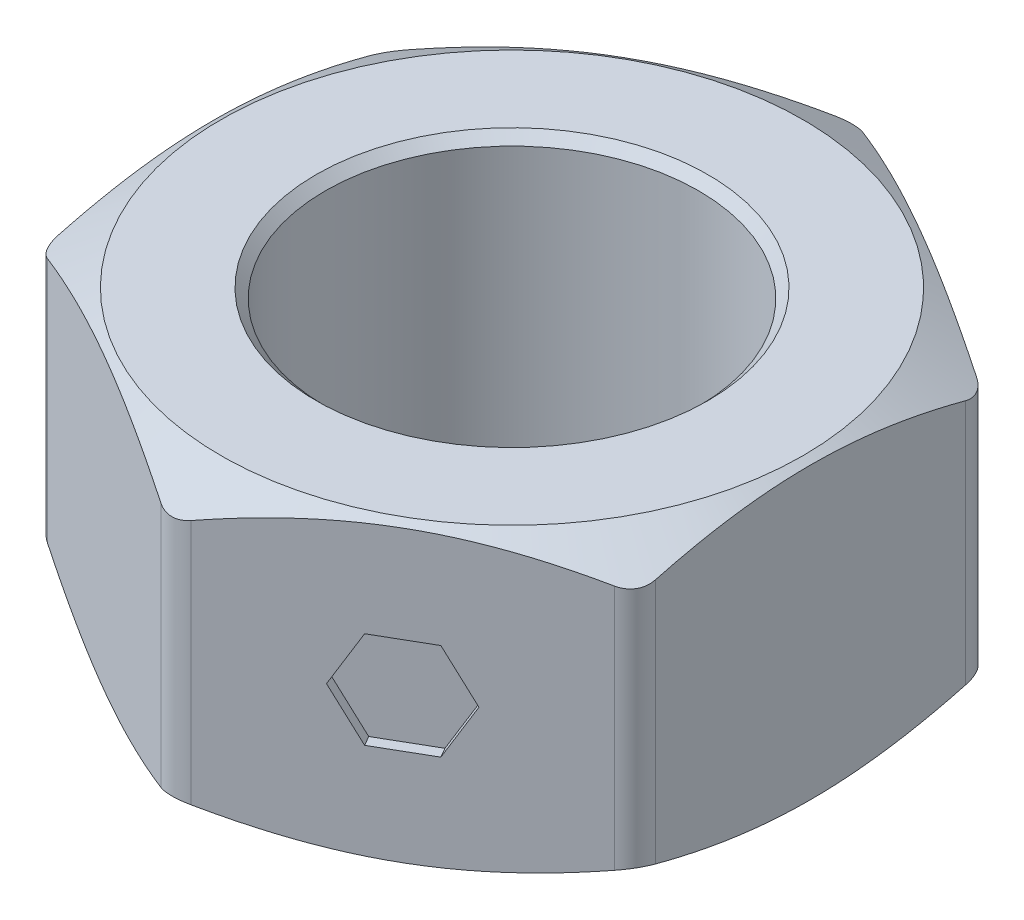
SolidWorks part; units mm, degrees
ref_plane "Front Plane" through (0, 0, 0) normal (0, 0, 1) x (1, 0, 0)
ref_plane "Top Plane" through (0, 0, 0) normal (0, 1, 0) x (1, 0, 0)
ref_plane "Right Plane" through (0, 0, 0) normal (1, 0, 0) x (0, 0, -1)
sketch "Sketch1" plane through (0, 0, 0) normal (0, 0, 1) x (1, 0, 0)
  line L0 (0, -2) -> (0, 2) construction
  line L1 (4, 0) -> (-4, 0) construction
  line L2 (2.5, -2) -> (-2.5, -2) construction
  line L3 (2.5, -2) -> (2.5, -1.2) construction
  point P4 (0, 0)
  point P8 (0, 0)
  point P11 (0, -2)
  dimension "Height" = 4
  dimension "Width" = 8
  dimension "Thread Size" = 5
  dimension "Thread Pitch" = 0.8
sketch "Sketch2" plane through (0, 0, 0) normal (0, 1, 0) x (1, 0, 0)
  line L1 (0, 4.6188) -> (-4, 2.3094)
  line L2 (-4, 2.3094) -> (-4, -2.3094)
  line L3 (-4, -2.3094) -> (0, -4.6188)
  line L4 (0, -4.6188) -> (4, -2.3094)
  line L5 (4, -2.3094) -> (4, 2.3094)
  line L6 (4, 2.3094) -> (0, 4.6188)
  circle A0 centre (0, 0) radius 4 construction
  circle A1 centre (0, 0) radius 2.5
  point P19 (0, -2.5)
extrude "Boss-Extrude1" add sketch "Sketch2" along normal up to vertex (2 mm away) and the other way up to vertex (2 mm away) up to point (0, 2, 0) other way up to point (0, -2, 0)
fillet "Fillet1" radius 0.4 6 edges at (-4, 0, -2.3094) (0, 0, -4.6188) (-4, 0, 2.3094) (4, 0, -2.3094) (4, 0, 2.3094) (0, 0, 4.6188)
sketch "Sketch3" plane through (0, 0, 0) normal (1, 0, 0) x (0, 0, -1)
  line L2 (3.9, -2) -> (4.6188, -1.585)
  line L3 (2.4249, -2) -> (4.5033, -2) construction
  line L4 (4.6188, 2) -> (4.6188, -2) construction
  line L5 (4.6188, -1.585) -> (4.6188, -2)
  line L6 (4.6188, -2) -> (3.9, -2)
  line L12 (2.4249, 2) -> (4.5033, 2) construction
  line L16 (2.5, 2) -> (2.5, 1.875)
  line L17 (2.5, 2) -> (2.625, 2)
  line L21 (2.5, -2) -> (2.5, -1.875)
  line L22 (-2.0785, -2) -> (2.0785, -2) construction
  line L24 (2.625, -2) -> (2.5, -2)
  line L25 (2.5, -1.875) -> (2.625, -2)
  line L26 (2.625, 2) -> (2.5, 1.875)
  line L28 (0, -2) -> (0, 2) construction
  line L29 (0, -2) -> (0, 2) construction
  line L33 (3.9, 2) -> (4.6188, 1.585)
  line L34 (3.9, 2) -> (4, 2) construction
  line L35 (2.5, 0) -> (4, 0) construction
  line L36 (2.5, -2) -> (2.5, 2) construction
  line L37 (2.4249, -2) -> (4.5033, -2) construction
  line L38 (4, 2) -> (4, 0) construction
  line L43 (4.6188, 1.585) -> (4.6188, 2)
  line L47 (4.6188, 2) -> (3.9, 2)
  point P1 (4, 0)
  point P14 (2.5, 0)
  dimension "D2" = 30
  dimension "D5" = 0.125
  dimension "D1" = 30
  dimension "D3" = 0.1
revolve "Cut-Revolve2" cut sketch "Sketch3" angle 360 about L0
sketch "Sketch12" plane through (2, 0, 3.4641) normal (0.5, 0, 0.866) x (0.866, 0, -0.5)
  line L0 (0, 1.9423) -> (0, 0.6474) construction
  line L1 (0, 0.6474) -> (0, -0.6474) construction
  line L2 (0, -0.6474) -> (0, -1.9423) construction
  line L5 (-0.7476, 0) -> (-0.3738, -0.6474)
  line L6 (-0.3738, -0.6474) -> (0.3738, -0.6474)
  line L7 (0.3738, -0.6474) -> (0.7476, 0)
  line L8 (0.7476, 0) -> (0.3738, 0.6474)
  line L9 (0.3738, 0.6474) -> (-0.3738, 0.6474)
  line L10 (-0.3738, 0.6474) -> (-0.7476, 0)
  circle A0 centre (0, 0) radius 0.6474 construction
  spline S0 degree 3 poles (2.0785, 1.6491) (1.3977, 1.8303) (0.7087, 1.9416) (-0.3443, 1.9426) (-0.6983, 1.9154) (-1.3936, 1.8138) (-1.7374, 1.7399) (-2.0785, 1.6491) knots 0 0 0 0 0.5 0.5 0.75 0.75 1 1 1 1 construction
  spline S1 degree 3 poles (-2.0785, -1.6491) (-1.3977, -1.8303) (-0.7087, -1.9416) (0.3443, -1.9426) (0.6983, -1.9154) (1.3936, -1.8138) (1.7374, -1.7399) (2.0785, -1.6491) knots 0 0 0 0 0.5 0.5 0.75 0.75 1 1 1 1 construction
  point P9 (0, 0)
extrude "Cut-Extrude2" cut sketch "Sketch12" against normal blind 0.15
sketch "Sketch5" plane through (0, 0, 0) normal (0, 1, 0) x (1, 0, 0)
  circle A2 centre (0, 0) radius 2.5 construction
  point P0 (0, -2.5)
sketch "Sketch6" [suppressed] plane through (0, 0, 0) normal (0, 0, 1) x (1, 0, 0)
  line L0 (2.5, 2) -> (2.5, -2)
  line L2 (0, -2) -> (4, -2) construction
  line L3 (2.5, -2) -> (0, -2)
  line L4 (0, -2) -> (0, 2)
  line L5 (0, -2) -> (0, 2) construction
  line L6 (0, 2) -> (2.5, 2)
revolve "Revolve2" [suppressed] add sketch "Sketch6" angle 360 about L4
sketch "Sketch7" [suppressed] plane through (0, -2, 0) normal (0, -1, 0) x (1, 0, 0)
  circle A2 centre (0, 0) radius 2.5
  circle A3 centre (0, 0) radius 2.5
  dimension "D1" = 0
curve "Helix/Spiral1" [suppressed] pitch 0.8 height 4.8 turns 6
sketch "Sketch8" [suppressed] plane through (0, 0, 0) normal (0, 0, 1) x (1, 0, 0)
  line L0 (2.5866, -1.95) -> (1.8938, -2.35) construction
  line L1 (1.8938, -2.35) -> (2.5866, -2.75) construction
  line L2 (2.5866, -2.75) -> (2.5866, -1.95) construction
  line L3 (1.9804, -2.3) -> (1.9804, -2.4)
  line L4 (2.5, -2) -> (2.5, -2.7) construction
  line L5 (2.5, -2.35) -> (2.5866, -2.35) construction
  line L6 (1.8938, -2.35) -> (1.9804, -2.35) construction
  line L7 (2.5433, -2.35) -> (2.5433, -2.725) construction
  line L8 (1.9804, -2.3) -> (2.5866, -1.95)
  line L9 (2.5866, -1.95) -> (2.5433, -2.725)
  line L10 (1.9804, -2.4) -> (2.5433, -2.725)
  dimension "D1" = 0.8
sweep "Cut-Sweep1" [suppressed] cut profiles "Sketch8" path "Helix/Spiral1"
sketch "Sketch9" [suppressed] plane through (0, 0, 0) normal (0, 0, 1) x (1, 0, 0)
  line L0 (0, 0.5) -> (0, -2)
  line L1 (0, 0.5) -> (0, 0.625)
  line L2 (0, -2) -> (2.5, -2)
  line L3 (2.5, -2) -> (2.625, -2)
  line L4 (2.625, -2) -> (0, 0.625)
  dimension "D1" = 0.125
revolve "Revolve3" [suppressed] add sketch "Sketch9" angle 360 about L0
sketch "Sketch11" [suppressed] plane through (0, 0, 0) normal (0, 0, 1) x (1, 0, 0)
  line L0 (0, 2) -> (0, -0.6)
  line L1 (0, -2) -> (0, 2) construction
  line L2 (0, -0.6) -> (2.625, 2)
  line L3 (2.625, 2) -> (0, 2)
  spline S0 degree 2 poles (-0.6818, -1.3554) (-1.0917, -1.3266) (-1.4003, -1.3) (-1.9804, -1.25) (-1.9804, -1.2) (-1.9804, -1.15) (-1.4003, -1.1) (-0.8203, -1.05) (0, -1) (0.8203, -0.95) (1.4003, -0.9) (1.9804, -0.85) (1.9804, -0.8) (1.9804, -0.75) (1.4003, -0.7) (0.8203, -0.65) (0, -0.6) (-0.8203, -0.55) (-1.4003, -0.5) (-1.9804, -0.45) (-1.9804, -0.4) (-1.9804, -0.35) (-1.4003, -0.3) (-0.8203, -0.25) (0, -0.2) (0.8203, -0.15) (1.4003, -0.1) (1.9804, -0.05) (1.9804, 0) (1.9804, 0.05) (1.4003, 0.1) (0.8203, 0.15) (0, 0.2) (-0.8203, 0.25) (-1.4003, 0.3) (-1.9804, 0.35) (-1.9804, 0.4) (-1.9804, 0.45) (-1.4003, 0.5) (-0.8203, 0.55) (0, 0.6) (0.8203, 0.65) (1.4003, 0.7) (1.9804, 0.75) (1.9804, 0.8) (1.9804, 0.85) (1.4003, 0.9) (0.8203, 0.95) (0, 1) (-0.8203, 1.05) (-1.4003, 1.1) (-1.9804, 1.15) (-1.9804, 1.2) (-1.9804, 1.25) (-1.4003, 1.3) (-0.8203, 1.35) (0, 1.4) (0.8203, 1.45) (1.4003, 1.5) (1.9804, 1.55) (1.9804, 1.6) (1.9804, 1.65) (1.4003, 1.7) (0.8203, 1.75) (0, 1.8) (-0.8203, 1.85) (-1.4003, 1.9) (-1.9804, 1.95) (-1.9804, 2) knots 0.329432 0.329432 0.329432 0.339286 0.339286 0.357143 0.357143 0.375 0.375 0.392857 0.392857 0.410714 0.410714 0.428571 0.428571 0.446429 0.446429 0.464286 0.464286 0.482143 0.482143 0.5 0.5 0.517857 0.517857 0.535714 0.535714 0.553571 0.553571 0.571429 0.571429 0.589286 0.589286 0.607143 0.607143 0.625 0.625 0.642857 0.642857 0.660714 0.660714 0.678571 0.678571 0.696429 0.696429 0.714286 0.714286 0.732143 0.732143 0.75 0.75 0.767857 0.767857 0.785714 0.785714 0.803571 0.803571 0.821429 0.821429 0.839286 0.839286 0.857143 0.857143 0.875 0.875 0.892857 0.892857 0.910714 0.910714 0.928571 0.928571 0.928571 weights 0.962349 0.957995 1 0.92388 1 0.92388 1 0.92388 1 0.92388 1 0.92388 1 0.92388 1 0.92388 1 0.92388 1 0.92388 1 0.92388 1 0.92388 1 0.92388 1 0.92388 1 0.92388 1 0.92388 1 0.92388 1 0.92388 1 0.92388 1 0.92388 1 0.92388 1 0.92388 1 0.92388 1 0.92388 1 0.92388 1 0.92388 1 0.92388 1 0.92388 1 0.92388 1 0.92388 1 0.92388 1 0.92388 1 0.92388 1 0.92388 1 construction
revolve "Revolve4" [suppressed] add sketch "Sketch11" angle 360 about L0
sketch "Sketch10" [suppressed] plane through (0, -2, 0) normal (0, -1, 0) x (1, 0, 0)
  circle A0 centre (0, 0) radius 2.625 construction
  circle A1 centre (0, 0) radius 2.625
extrude "Boss-Extrude2" [suppressed] add sketch "Sketch10" against normal up to surface (4 mm away)
combine bodies "Combine1" [suppressed] operation type subtract main body 110 bodies to subtract 112
equation "\"D5@Sketch3\"=\"Thread Size@Sketch1\"*.025"
equation "\"D4@Helix/Spiral1\" = \"Thread Pitch@Sketch1\""
equation "\"D3@Helix/Spiral1\"=\"Height@Sketch1\"+\"Thread Pitch@Sketch1\""
equation "\"D1@Sketch8\" = \"Thread Pitch@Sketch1\""
equation "\"D2@Sketch8\" = \"Thread Pitch@Sketch1\" / 8"
equation "\"D1@Sketch9\"=\"Thread Size@Sketch1\" * .025"
equation "\"D1@Fillet1\"=\"Width@Sketch1\" * .05"
equation "\"D3@Sketch3\"=\"Width@Sketch1\"*.0125"
equation "\"D1@Cut-Extrude2\"=((\"Width@Sketch1\"-\"Thread Size@Sketch1\")/2)*.1"
